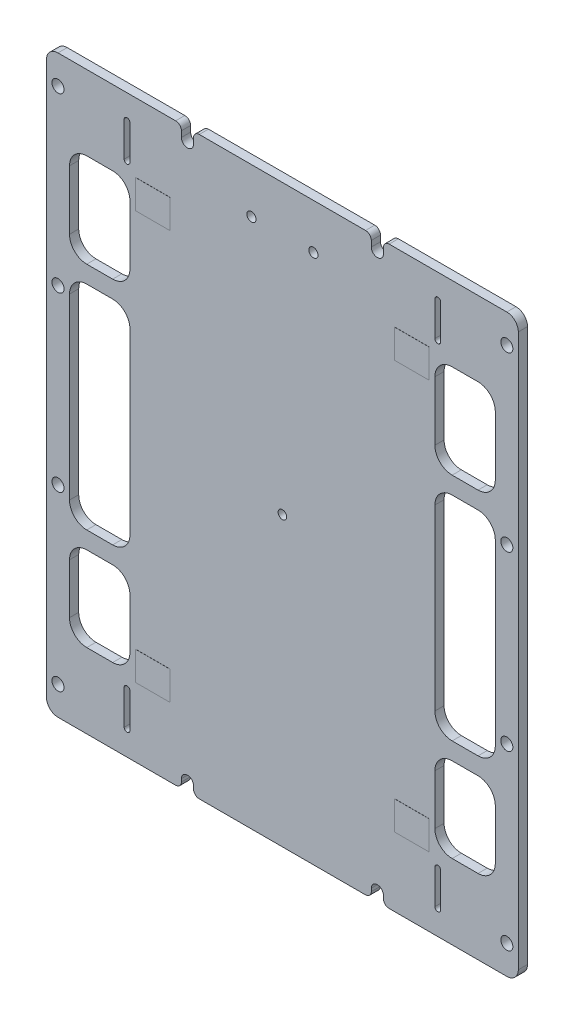
SolidWorks part; units mm, degrees
material "FR4_stuffedProtoboard"
ref_plane "Front Plane" through (0, 0, 0) normal (0, 0, 1) x (1, 0, 0)
ref_plane "Top Plane" through (0, 0, 0) normal (0, 1, 0) x (1, 0, 0)
ref_plane "Right Plane" through (0, 0, 0) normal (1, 0, 0) x (0, 0, -1)
sketch "Sketch1" plane through (0, 0, 0) normal (0, 0, 1) x (1, 0, 0)
  line L1 (-39, -50) -> (39, -50)
  line L2 (-41, -48) -> (-41, 48)
  line L3 (-39, 50) -> (39, 50)
  line L4 (41, -48) -> (41, 48)
  line L5 (-41, -50) -> (41, 50) construction
  line L6 (-41, 50) -> (41, -50) construction
  arc A0 (-39, -50) -> (-41, -48) centre (-39, -48) cw
  arc A1 (39, -50) -> (41, -48) centre (39, -48) ccw
  arc A2 (39, 50) -> (41, 48) centre (39, 48) cw
  arc A3 (-41, 48) -> (-39, 50) centre (-39, 48) cw
  point P0 (0, 0)
  dimension "D3" = 2
  dimension "D1" = 100
  dimension "D2" = 82
extrude "boardOutline" add sketch "Sketch1" along normal blind 1.6
sketch "Sketch2" plane through (0, 0, 1.6) normal (0, 0, 1) x (1, 0, 0)
  line L0 (39, 50) -> (-39, 50) construction
  line L1 (-41, 48) -> (-41, -48) construction
  line L3 (-37.5, 44.2) -> (-37.5, 4.2) construction
  circle A0 centre (0, 0) radius 0.75
  circle A1 centre (-37.5, 44.2) radius 1.05 construction
  circle A2 centre (37.5, 44.2) radius 1.05 construction
  circle A3 centre (37.5, 4.2) radius 1.05 construction
  circle A4 centre (37.5, -35.8) radius 1.05 construction
  circle A5 centre (-37.5, 4.2) radius 1.05 construction
  circle A6 centre (-37.5, -35.8) radius 1.05 construction
  circle A7 centre (-5.38, 42.15) radius 0.8
  circle A8 centre (5.39, 42.15) radius 0.8
  dimension "D1" = 1.5
  dimension "D2" = 2.1
  dimension "D9" = 10.77
  dimension "D7" = 1.6
  dimension "D11" = 7.85
  dimension "D12" = 35.62
  dimension "D3" = 5.8
  dimension "D4" = 3.5
  dimension "D8" = 40
  dimension "D10" = 37.5
  dimension "D5" = 2
  dimension "D6" = 3
extrude "componentHoles" cut sketch "Sketch2" against normal through all
sketch "Sketch4" plane through (0, 0, 1.6) normal (0, 0, 1) x (1, 0, 0)
  line L0 (-27, 39.75) -> (-27, 45.75) construction
  line L1 (-27.5, 39.75) -> (-27.5, 45.75)
  line L2 (-26.5, 39.75) -> (-26.5, 45.75)
  line L3 (39, 50) -> (-39, 50) construction
  line L4 (-41, 48) -> (-41, -48) construction
  line L5 (27, 39.75) -> (27, 45.75) construction
  line L6 (26.5, 39.75) -> (26.5, 45.75)
  line L7 (27.5, 39.75) -> (27.5, 45.75)
  line L8 (27, -45.75) -> (27, -39.75) construction
  line L9 (26.5, -45.75) -> (26.5, -39.75)
  line L10 (27.5, -45.75) -> (27.5, -39.75)
  line L11 (-27, -45.75) -> (-27, -39.75) construction
  line L12 (-27.5, -45.75) -> (-27.5, -39.75)
  line L13 (-26.5, -45.75) -> (-26.5, -39.75)
  line L14 (-27, 39.75) -> (27, 39.75) construction
  line L15 (-39, -50) -> (39, -50) construction
  arc A0 (-27.5, 39.75) -> (-26.5, 39.75) centre (-27, 39.75) ccw
  arc A1 (-26.5, 45.75) -> (-27.5, 45.75) centre (-27, 45.75) ccw
  arc A2 (26.5, 39.75) -> (27.5, 39.75) centre (27, 39.75) ccw
  arc A3 (27.5, 45.75) -> (26.5, 45.75) centre (27, 45.75) ccw
  arc A4 (26.5, -45.75) -> (27.5, -45.75) centre (27, -45.75) ccw
  arc A5 (27.5, -39.75) -> (26.5, -39.75) centre (27, -39.75) ccw
  arc A6 (-27.5, -45.75) -> (-26.5, -45.75) centre (-27, -45.75) ccw
  arc A7 (-26.5, -39.75) -> (-27.5, -39.75) centre (-27, -39.75) ccw
  point P2 (-27, 42.75)
  point P16 (27, 42.75)
  point P23 (27, -42.75)
  point P30 (-27, -42.75)
  dimension "D1" = 4.25
  dimension "D2" = 13.5
  dimension "D3" = 1
  dimension "D4" = 6
  dimension "D7" = 54
  dimension "D8" = 14
  dimension "D9" = 4.25
  dimension "D10" = 4.25
  dimension "D5" = 2
  dimension "D6" = 2
extrude "solarCellContactHoles" cut sketch "Sketch4" against normal blind 1.6
sketch "Sketch3" plane through (0, 0, 1.6) normal (0, 0, 1) x (1, 0, 0)
  line L1 (-34, 37) -> (-29.5, 37)
  line L2 (-37, 34) -> (-37, 23.7)
  line L3 (-34, 20.7) -> (-29.5, 20.7)
  line L4 (-26.5, 34) -> (-26.5, 23.7)
  line L5 (-41, 48) -> (-41, -48) construction
  line L6 (-29.5, -22.3) -> (-34, -22.3)
  line L9 (0, 50) -> (0, -50) construction
  line L10 (39, 50) -> (-39, 50) construction
  line L11 (-39, -50) -> (39, -50) construction
  line L12 (-26.5, -25.3) -> (-26.5, -34)
  line L13 (-29.5, -37) -> (-34, -37)
  line L14 (-37, -25.3) -> (-37, -34)
  line L19 (-29.5, -19.3) -> (-34, -19.3)
  line L25 (-26.5, -16.3) -> (-26.5, 14.7)
  line L26 (-29.5, 17.7) -> (-34, 17.7)
  line L27 (-37, -16.3) -> (-37, 14.7)
  arc A0 (-37, 23.7) -> (-34, 20.7) centre (-34, 23.7) ccw
  arc A1 (-29.5, 20.7) -> (-26.5, 23.7) centre (-29.5, 23.7) ccw
  arc A2 (-29.5, 37) -> (-26.5, 34) centre (-29.5, 34) cw
  arc A3 (-34, 37) -> (-37, 34) centre (-34, 34) ccw
  arc A4 (-29.5, -19.3) -> (-26.5, -16.3) centre (-29.5, -16.3) ccw
  arc A5 (-26.5, -34) -> (-29.5, -37) centre (-29.5, -34) cw
  arc A6 (-34, -37) -> (-37, -34) centre (-34, -34) cw
  arc A7 (-34, -22.3) -> (-37, -25.3) centre (-34, -25.3) ccw
  arc A8 (-29.5, -22.3) -> (-26.5, -25.3) centre (-29.5, -25.3) cw
  arc A17 (-34, -19.3) -> (-37, -16.3) centre (-34, -16.3) cw
  arc A18 (-34, 17.7) -> (-37, 14.7) centre (-34, 14.7) ccw
  arc A19 (-26.5, 14.7) -> (-29.5, 17.7) centre (-29.5, 14.7) ccw
  point P12 (-26.5, 20.7)
  point P15 (-26.5, 37)
  point P18 (-37, 37)
  dimension "D5" = 3
  dimension "D10" = 13
  dimension "D7" = 3
  dimension "D11" = 3
  dimension "D1" = 10.5
  dimension "D2" = 29.3
  dimension "D3" = 13
  dimension "D4" = 4
  dimension "D8" = 3
  dimension "D9" = 3
  dimension "D6" = 37
extrude "windows_1side" cut sketch "Sketch3" against normal through all
sketch "Sketch5" plane through (0, 0, 1.6) normal (0, 0, 1) x (1, 0, 0)
  line L0 (-41, 48) -> (-41, -48) construction
  line L1 (-25.5, 38) -> (-19.5, 38)
  line L2 (-25.5, 38) -> (-25.5, 33)
  line L3 (-25.5, 33) -> (-19.5, 33)
  line L4 (-19.5, 38) -> (-19.5, 33)
  line L5 (39, 50) -> (-39, 50) construction
  line L6 (19.5, 38) -> (19.5, 33)
  line L7 (25.5, 38) -> (25.5, 33)
  line L8 (19.5, 33) -> (25.5, 33)
  line L9 (19.5, 38) -> (25.5, 38)
  line L10 (19.5, -33) -> (19.5, -38)
  line L11 (25.5, -33) -> (25.5, -38)
  line L12 (19.5, -38) -> (25.5, -38)
  line L13 (19.5, -33) -> (25.5, -33)
  line L14 (-25.5, -33) -> (-25.5, -38)
  line L15 (-19.5, -33) -> (-19.5, -38)
  line L16 (-25.5, -38) -> (-19.5, -38)
  line L17 (-25.5, -33) -> (-19.5, -33)
  line L18 (-25.5, 38) -> (19.5, 38) construction
  line L19 (-25.5, 38) -> (-25.5, -33) construction
  dimension "D1" = 5
  dimension "D2" = 6
  dimension "D3" = 15.5
  dimension "D4" = 12
  dimension "D7" = 45
  dimension "D8" = 71
  dimension "D5" = 2
  dimension "D6" = 2
extrude "contactPads" add sketch "Sketch5" along normal blind 0.02
hole_wizard "M2 Clearance Hole1" positions "Sketch6" profile "Sketch7" hole size "M2" standard "ANSI Metric" end condition through all
sketch "Sketch6" plane through (0, 0, 0) normal (0, 0, -1) x (-1, 0, 0)
  line L5 (39, -50) -> (39, -45) construction
  line L6 (39, -50) -> (-39, -50) construction
  line L7 (39, -45) -> (39, -15) construction
  line L8 (39, -15) -> (39, 15) construction
  line L9 (39, 15) -> (39, 45) construction
  line L10 (39, 45) -> (39, 50) construction
  line L11 (-39, 50) -> (39, 50) construction
  line L15 (37, -27.0602) -> (41, -27.0602) construction
  line L16 (37, -25.3) -> (37, -34) construction
  line L17 (41, 48) -> (41, -48) construction
  point P0 (39, 45)
  point P27 (39, -15)
  point P36 (39, -45)
  point P38 (39, 15)
  point P73 (39, -27.0602)
  dimension "D2" = 5
sketch "Sketch7" plane through (-39, 45, 0) normal (1, 0, 0) x (0, 1, 0)
  line L0 (0, 0) -> (0, 1.62)
  line L1 (0, 1.62) -> (1.05, 1.62)
  line L2 (1.05, 1.62) -> (1.05, 0)
  line L5 (1.05, 0) -> (0, 0)
  line L11 (0, -6.35) -> (0, 107.95) construction
  dimension "Thru Hole Dia." = 2.1
  dimension "Thru Hole Depth" = 1.62
sketch "Sketch10" plane through (0, 0, 0) normal (0, 0, -1) x (-1, 0, 0)
  line L0 (16.5, 48) -> (16.5, 55.0732) construction
  line L1 (15.45, 48) -> (15.45, 55.0732)
  line L2 (17.55, 48) -> (17.55, 55.0732)
  line L3 (16.5, -48.5) -> (16.5, -55.5732) construction
  line L4 (17.55, -48.5) -> (17.55, -55.5732)
  line L5 (15.45, -48.5) -> (15.45, -55.5732)
  line L6 (41, 48) -> (41, -48) construction
  line L8 (39, -50) -> (-39, -50) construction
  line L9 (-39, 50) -> (39, 50) construction
  arc A0 (15.45, 48) -> (17.55, 48) centre (16.5, 48) ccw
  arc A1 (17.55, 55.0732) -> (15.45, 55.0732) centre (16.5, 55.0732) ccw
  arc A2 (17.55, -48.5) -> (15.45, -48.5) centre (16.5, -48.5) ccw
  arc A3 (15.45, -55.5732) -> (17.55, -55.5732) centre (16.5, -55.5732) ccw
  point P2 (16.5, 51.5366)
  point P7 (16.5, -52.0366)
  point P14 (0, 0)
  point P23 (13.1916, 50)
  dimension "D1" = 1.05
  dimension "D2" = 24.5
  dimension "D3" = 2
  dimension "D4" = 1.5
extrude "Cut-Extrude1" cut sketch "Sketch10" against normal through all both and the other way through all
fillet "Fillet3" radius 1 4 edges at (-17.55, 50, 0.8) (-15.45, 50, 0.8) (-15.45, -50, 0.8) (-17.55, -50, 0.8)
mirror "Mirror1" about plane through (0, 0, 0) normal (1, 0, 0) of "Cut-Extrude1", "Fillet3", "windows_1side", "M2 Clearance Hole1"
sketch "thermalContact" plane through (0, 0, 1.6) normal (0, 0, 1) x (1, 0, 0)
  line L0 (-37, 43) -> (-37, 23.7) construction
  line L1 (-34, 20.7) -> (-21, 20.7) construction
  line L2 (-18, 23.7) -> (-18, 43) construction
  line L3 (-21, 46) -> (-34, 46) construction
  line L4 (-41, 48) -> (-41, -162)
  line L5 (39, 50) -> (-39, 50)
  line L6 (41, -162) -> (41, 48)
  line L7 (-39, -164) -> (39, -164)
  line L8 (-41, 48) -> (-41, -162)
  line L9 (39, 50) -> (-39, 50)
  line L10 (41, -162) -> (41, 48)
  line L11 (-39, -164) -> (39, -164)
  line L12 (-37, 43) -> (-37, 23.7)
  line L13 (-34, 20.7) -> (-21, 20.7)
  line L14 (-18, 23.7) -> (-18, 43)
  line L15 (-21, 46) -> (-34, 46)
  line L16 (18, 43) -> (18, 23.7) construction
  line L17 (21, 20.7) -> (34, 20.7) construction
  line L18 (37, 23.7) -> (37, 43) construction
  line L19 (34, 46) -> (21, 46) construction
  line L20 (18, 43) -> (18, 23.7)
  line L21 (21, 20.7) -> (34, 20.7)
  line L22 (37, 23.7) -> (37, 43)
  line L23 (34, 46) -> (21, 46)
  line L24 (-12, -47) -> (12, -47) construction
  line L25 (15, -44) -> (15, -25.3) construction
  line L26 (12, -22.3) -> (-12, -22.3) construction
  line L27 (-15, -25.3) -> (-15, -44) construction
  line L28 (-12, -47) -> (12, -47)
  line L29 (15, -44) -> (15, -25.3)
  line L30 (12, -22.3) -> (-12, -22.3)
  line L31 (-15, -25.3) -> (-15, -44)
  line L32 (-37, -25.3) -> (-37, -44) construction
  line L33 (-34, -47) -> (-21, -47) construction
  line L34 (-18, -44) -> (-18, -25.3) construction
  line L35 (-21, -22.3) -> (-34, -22.3) construction
  line L36 (-37, -25.3) -> (-37, -44)
  line L37 (-34, -47) -> (-21, -47)
  line L38 (-18, -44) -> (-18, -25.3)
  line L39 (-21, -22.3) -> (-34, -22.3)
  line L40 (18, -25.3) -> (18, -44) construction
  line L41 (21, -47) -> (34, -47) construction
  line L42 (37, -44) -> (37, -25.3) construction
  line L43 (34, -22.3) -> (21, -22.3) construction
  line L44 (18, -25.3) -> (18, -44)
  line L45 (21, -47) -> (34, -47)
  line L46 (37, -44) -> (37, -25.3)
  line L47 (34, -22.3) -> (21, -22.3)
  line L48 (-12, -19.3) -> (12, -19.3) construction
  line L49 (15, -16.3) -> (15, 14.7) construction
  line L50 (12, 17.7) -> (-12, 17.7) construction
  line L51 (-15, 14.7) -> (-15, -16.3) construction
  line L52 (-12, -19.3) -> (12, -19.3)
  line L53 (15, -16.3) -> (15, 14.7)
  line L54 (12, 17.7) -> (-12, 17.7)
  line L55 (-15, 14.7) -> (-15, -16.3)
  line L56 (-21, 17.7) -> (-34, 17.7) construction
  line L57 (-37, 14.7) -> (-37, -16.3) construction
  line L58 (-34, -19.3) -> (-21, -19.3) construction
  line L59 (-18, -16.3) -> (-18, 14.7) construction
  line L60 (-21, 17.7) -> (-34, 17.7)
  line L61 (-37, 14.7) -> (-37, -16.3)
  line L62 (-34, -19.3) -> (-21, -19.3)
  line L63 (-18, -16.3) -> (-18, 14.7)
  line L64 (21, -19.3) -> (34, -19.3) construction
  line L65 (37, -16.3) -> (37, 14.7) construction
  line L66 (34, 17.7) -> (21, 17.7) construction
  line L67 (18, 14.7) -> (18, -16.3) construction
  line L68 (21, -19.3) -> (34, -19.3)
  line L69 (37, -16.3) -> (37, 14.7)
  line L70 (34, 17.7) -> (21, 17.7)
  line L71 (18, 14.7) -> (18, -16.3)
  line L72 (-12, 20.7) -> (12, 20.7) construction
  line L73 (15, 23.7) -> (15, 43) construction
  line L74 (12, 46) -> (-12, 46) construction
  line L75 (-15, 43) -> (-15, 23.7) construction
  line L76 (-12, 20.7) -> (12, 20.7)
  line L77 (15, 23.7) -> (15, 43)
  line L78 (12, 46) -> (-12, 46)
  line L79 (-15, 43) -> (-15, 23.7)
  line L80 (-21, -50) -> (-34, -50) construction
  line L81 (-37, -53) -> (-37, -61) construction
  line L82 (-34, -64) -> (-21, -64) construction
  line L83 (-18, -61) -> (-18, -53) construction
  line L84 (-21, -50) -> (-34, -50)
  line L85 (-37, -53) -> (-37, -61)
  line L86 (-34, -64) -> (-21, -64)
  line L87 (-18, -61) -> (-18, -53)
  line L88 (-15, -53) -> (-15, -61) construction
  line L89 (-12, -64) -> (12, -64) construction
  line L90 (15, -61) -> (15, -53) construction
  line L91 (12, -50) -> (-12, -50) construction
  line L92 (-15, -53) -> (-15, -61)
  line L93 (-12, -64) -> (12, -64)
  line L94 (15, -61) -> (15, -53)
  line L95 (12, -50) -> (-12, -50)
  line L96 (18, -53) -> (18, -61) construction
  line L97 (21, -64) -> (34, -64) construction
  line L98 (37, -61) -> (37, -53) construction
  line L99 (34, -50) -> (21, -50) construction
  line L100 (18, -53) -> (18, -61)
  line L101 (21, -64) -> (34, -64)
  line L102 (37, -61) -> (37, -53)
  line L103 (34, -50) -> (21, -50)
  arc A0 (-34, 46) -> (-37, 43) centre (-34, 43) ccw construction
  arc A1 (-37, 23.7) -> (-34, 20.7) centre (-34, 23.7) ccw construction
  arc A2 (-21, 20.7) -> (-18, 23.7) centre (-21, 23.7) ccw construction
  arc A3 (-18, 43) -> (-21, 46) centre (-21, 43) ccw construction
  arc A4 (-39, 50) -> (-41, 48) centre (-39, 48) ccw
  arc A5 (41, 48) -> (39, 50) centre (39, 48) ccw
  arc A6 (39, -164) -> (41, -162) centre (39, -162) ccw
  arc A7 (-41, -162) -> (-39, -164) centre (-39, -162) ccw
  arc A8 (-39, 50) -> (-41, 48) centre (-39, 48) ccw
  arc A9 (41, 48) -> (39, 50) centre (39, 48) ccw
  arc A10 (39, -164) -> (41, -162) centre (39, -162) ccw
  arc A11 (-41, -162) -> (-39, -164) centre (-39, -162) ccw
  arc A12 (-34, 46) -> (-37, 43) centre (-34, 43) ccw
  arc A13 (-37, 23.7) -> (-34, 20.7) centre (-34, 23.7) ccw
  arc A14 (-21, 20.7) -> (-18, 23.7) centre (-21, 23.7) ccw
  arc A15 (-18, 43) -> (-21, 46) centre (-21, 43) ccw
  arc A16 (21, 46) -> (18, 43) centre (21, 43) ccw construction
  arc A17 (18, 23.7) -> (21, 20.7) centre (21, 23.7) ccw construction
  arc A18 (34, 20.7) -> (37, 23.7) centre (34, 23.7) ccw construction
  arc A19 (37, 43) -> (34, 46) centre (34, 43) ccw construction
  arc A20 (21, 46) -> (18, 43) centre (21, 43) ccw
  arc A21 (18, 23.7) -> (21, 20.7) centre (21, 23.7) ccw
  arc A22 (34, 20.7) -> (37, 23.7) centre (34, 23.7) ccw
  arc A23 (37, 43) -> (34, 46) centre (34, 43) ccw
  arc A24 (-15, -44) -> (-12, -47) centre (-12, -44) ccw construction
  arc A25 (12, -47) -> (15, -44) centre (12, -44) ccw construction
  arc A26 (15, -25.3) -> (12, -22.3) centre (12, -25.3) ccw construction
  arc A27 (-12, -22.3) -> (-15, -25.3) centre (-12, -25.3) ccw construction
  arc A28 (-15, -44) -> (-12, -47) centre (-12, -44) ccw
  arc A29 (12, -47) -> (15, -44) centre (12, -44) ccw
  arc A30 (15, -25.3) -> (12, -22.3) centre (12, -25.3) ccw
  arc A31 (-12, -22.3) -> (-15, -25.3) centre (-12, -25.3) ccw
  arc A32 (-34, -22.3) -> (-37, -25.3) centre (-34, -25.3) ccw construction
  arc A33 (-37, -44) -> (-34, -47) centre (-34, -44) ccw construction
  arc A34 (-21, -47) -> (-18, -44) centre (-21, -44) ccw construction
  arc A35 (-18, -25.3) -> (-21, -22.3) centre (-21, -25.3) ccw construction
  arc A36 (-34, -22.3) -> (-37, -25.3) centre (-34, -25.3) ccw
  arc A37 (-37, -44) -> (-34, -47) centre (-34, -44) ccw
  arc A38 (-21, -47) -> (-18, -44) centre (-21, -44) ccw
  arc A39 (-18, -25.3) -> (-21, -22.3) centre (-21, -25.3) ccw
  arc A40 (21, -22.3) -> (18, -25.3) centre (21, -25.3) ccw construction
  arc A41 (18, -44) -> (21, -47) centre (21, -44) ccw construction
  arc A42 (34, -47) -> (37, -44) centre (34, -44) ccw construction
  arc A43 (37, -25.3) -> (34, -22.3) centre (34, -25.3) ccw construction
  arc A44 (21, -22.3) -> (18, -25.3) centre (21, -25.3) ccw
  arc A45 (18, -44) -> (21, -47) centre (21, -44) ccw
  arc A46 (34, -47) -> (37, -44) centre (34, -44) ccw
  arc A47 (37, -25.3) -> (34, -22.3) centre (34, -25.3) ccw
  arc A48 (-15, -16.3) -> (-12, -19.3) centre (-12, -16.3) ccw construction
  arc A49 (12, -19.3) -> (15, -16.3) centre (12, -16.3) ccw construction
  arc A50 (15, 14.7) -> (12, 17.7) centre (12, 14.7) ccw construction
  arc A51 (-12, 17.7) -> (-15, 14.7) centre (-12, 14.7) ccw construction
  arc A52 (-15, -16.3) -> (-12, -19.3) centre (-12, -16.3) ccw
  arc A53 (12, -19.3) -> (15, -16.3) centre (12, -16.3) ccw
  arc A54 (15, 14.7) -> (12, 17.7) centre (12, 14.7) ccw
  arc A55 (-12, 17.7) -> (-15, 14.7) centre (-12, 14.7) ccw
  arc A56 (-18, 14.7) -> (-21, 17.7) centre (-21, 14.7) ccw construction
  arc A57 (-34, 17.7) -> (-37, 14.7) centre (-34, 14.7) ccw construction
  arc A58 (-37, -16.3) -> (-34, -19.3) centre (-34, -16.3) ccw construction
  arc A59 (-21, -19.3) -> (-18, -16.3) centre (-21, -16.3) ccw construction
  arc A60 (-18, 14.7) -> (-21, 17.7) centre (-21, 14.7) ccw
  arc A61 (-34, 17.7) -> (-37, 14.7) centre (-34, 14.7) ccw
  arc A62 (-37, -16.3) -> (-34, -19.3) centre (-34, -16.3) ccw
  arc A63 (-21, -19.3) -> (-18, -16.3) centre (-21, -16.3) ccw
  arc A64 (18, -16.3) -> (21, -19.3) centre (21, -16.3) ccw construction
  arc A65 (34, -19.3) -> (37, -16.3) centre (34, -16.3) ccw construction
  arc A66 (37, 14.7) -> (34, 17.7) centre (34, 14.7) ccw construction
  arc A67 (21, 17.7) -> (18, 14.7) centre (21, 14.7) ccw construction
  arc A68 (18, -16.3) -> (21, -19.3) centre (21, -16.3) ccw
  arc A69 (34, -19.3) -> (37, -16.3) centre (34, -16.3) ccw
  arc A70 (37, 14.7) -> (34, 17.7) centre (34, 14.7) ccw
  arc A71 (21, 17.7) -> (18, 14.7) centre (21, 14.7) ccw
  arc A72 (-15, 23.7) -> (-12, 20.7) centre (-12, 23.7) ccw construction
  arc A73 (12, 20.7) -> (15, 23.7) centre (12, 23.7) ccw construction
  arc A74 (15, 43) -> (12, 46) centre (12, 43) ccw construction
  arc A75 (-12, 46) -> (-15, 43) centre (-12, 43) ccw construction
  arc A76 (-15, 23.7) -> (-12, 20.7) centre (-12, 23.7) ccw
  arc A77 (12, 20.7) -> (15, 23.7) centre (12, 23.7) ccw
  arc A78 (15, 43) -> (12, 46) centre (12, 43) ccw
  arc A79 (-12, 46) -> (-15, 43) centre (-12, 43) ccw
  arc A80 (-34, -50) -> (-37, -53) centre (-34, -53) ccw construction
  arc A81 (-37, -61) -> (-34, -64) centre (-34, -61) ccw construction
  arc A82 (-21, -64) -> (-18, -61) centre (-21, -61) ccw construction
  arc A83 (-18, -53) -> (-21, -50) centre (-21, -53) ccw construction
  arc A84 (-34, -50) -> (-37, -53) centre (-34, -53) ccw
  arc A85 (-37, -61) -> (-34, -64) centre (-34, -61) ccw
  arc A86 (-21, -64) -> (-18, -61) centre (-21, -61) ccw
  arc A87 (-18, -53) -> (-21, -50) centre (-21, -53) ccw
  arc A88 (-15, -61) -> (-12, -64) centre (-12, -61) ccw construction
  arc A89 (12, -64) -> (15, -61) centre (12, -61) ccw construction
  arc A90 (15, -53) -> (12, -50) centre (12, -53) ccw construction
  arc A91 (-12, -50) -> (-15, -53) centre (-12, -53) ccw construction
  arc A92 (-15, -61) -> (-12, -64) centre (-12, -61) ccw
  arc A93 (12, -64) -> (15, -61) centre (12, -61) ccw
  arc A94 (15, -53) -> (12, -50) centre (12, -53) ccw
  arc A95 (-12, -50) -> (-15, -53) centre (-12, -53) ccw
  arc A96 (21, -50) -> (18, -53) centre (21, -53) ccw construction
  arc A97 (18, -61) -> (21, -64) centre (21, -61) ccw construction
  arc A98 (34, -64) -> (37, -61) centre (34, -61) ccw construction
  arc A99 (37, -53) -> (34, -50) centre (34, -53) ccw construction
  arc A100 (18, -61) -> (21, -64) centre (21, -61) ccw
  arc A101 (34, -64) -> (37, -61) centre (34, -61) ccw
  arc A102 (37, -53) -> (34, -50) centre (34, -53) ccw
  arc A103 (21, -50) -> (18, -53) centre (21, -53) ccw
  dimension "D1" = 0
